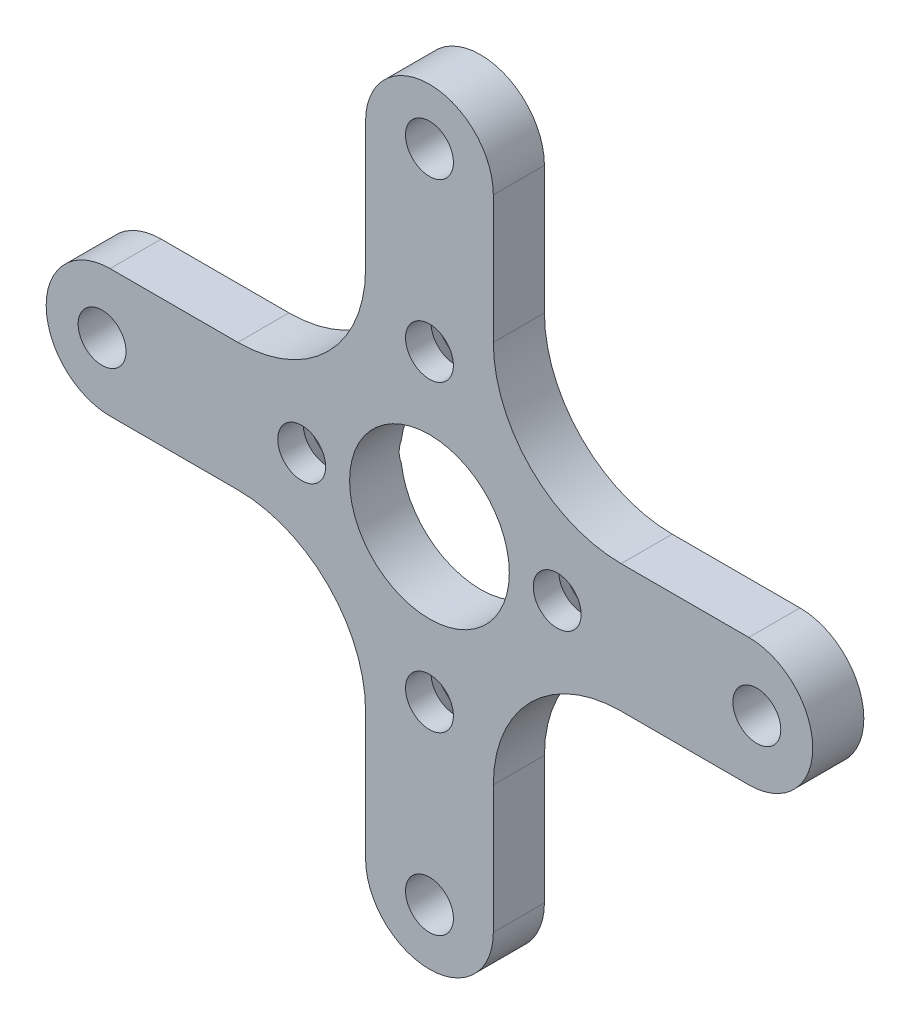
SolidWorks part; units mm, degrees
ref_plane "Спереди" through (0, 0, 0) normal (0, 0, 1) x (1, 0, 0)
ref_plane "Сверху" through (0, 0, 0) normal (0, 1, 0) x (1, 0, 0)
ref_plane "Справа" through (0, 0, 0) normal (1, 0, 0) x (0, 0, -1)
sketch "Эскиз1" plane through (0, 0, 0) normal (0, 0, 1) x (1, 0, 0)
  line L0 (-4, 20) -> (-4, 12)
  line L1 (-12, 4) -> (-20, 4)
  line L2 (-20, -4) -> (-12, -4)
  line L3 (-4, -12) -> (-4, -20)
  line L4 (4, -20) -> (4, -12)
  line L5 (12, -4) -> (20, -4)
  line L6 (4, 20) -> (4, 12)
  line L7 (12, 4) -> (20, 4)
  arc A0 (-4, 20) -> (4, 20) centre (0, 20) cw
  arc A1 (-4, 12) -> (-12, 4) centre (-12, 12) cw
  arc A2 (-20, 4) -> (-20, -4) centre (-20, 0) ccw
  arc A4 (-4, -20) -> (4, -20) centre (0, -20) ccw
  arc A5 (4, -12) -> (12, -4) centre (12, -12) cw
  arc A6 (4, 12) -> (12, 4) centre (12, 12) ccw
  arc A7 (20, 4) -> (20, -4) centre (20, 0) cw
  arc A8 (-12, -4) -> (-4, -12) centre (-12, -12) cw
  circle A13 centre (0, 0) radius 5
  circle A14 centre (0, 0) radius 8 construction
  circle A15 centre (0, 0) radius 9.5 construction
  circle A16 centre (0, 9.5) radius 1.5
  circle A17 centre (0, -9.5) radius 1.5
  circle A18 centre (-8, 0) radius 1.5
  circle A19 centre (8, 0) radius 1.5
  circle A20 centre (0, 0) radius 24 construction
  circle A22 centre (0, 20.5) radius 1.5
  circle A23 centre (20.5, 0) radius 1.5
  circle A24 centre (-20.5, 0) radius 1.5
  circle A25 centre (0, -20.5) radius 1.5
  circle A26 centre (0, 0) radius 20.5 construction
  dimension "D2" = 3
  dimension "D3" = 10
  dimension "D4" = 16
  dimension "D5" = 19
  dimension "D6" = 48
  dimension "D7" = 41
  dimension "D8" = 8
  dimension "D1" = 8
extrude "Бобышка-Вытянуть1" add sketch "Эскиз1" along normal blind 3.2
chamfer "Фаска1" distance 1.6 angle 45 4 edges at (1.5, -9.5, 0) (1.5, 9.5, 0) (-6.5, 0, 0) (9.5, 0, 0)
scale "Масштаб1" scale about centroid uniform scaling yes scale factor 0.5
